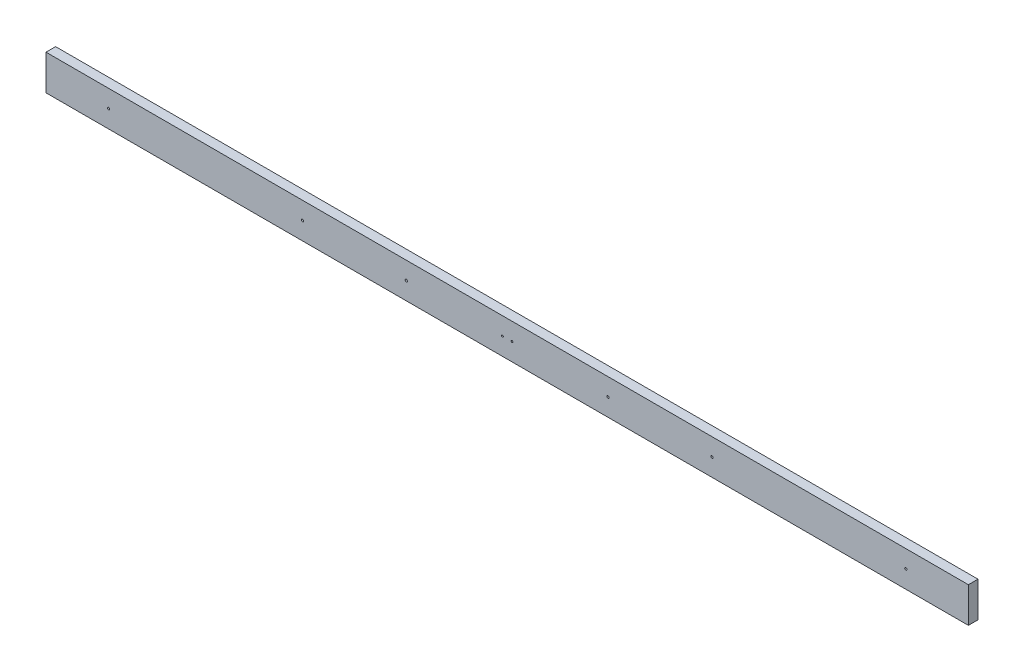
SolidWorks part; units mm, degrees
ref_plane "Front Plane" through (0, 0, 0) normal (0, 0, 1) x (1, 0, 0)
ref_plane "Top Plane" through (0, 0, 0) normal (0, 1, 0) x (1, 0, 0)
ref_plane "Right Plane" through (0, 0, 0) normal (1, 0, 0) x (0, 0, -1)
sketch "Sketch1" plane through (0, 0, 0) normal (0, 0, 1) x (1, 0, 0)
  line L1 (-1828.8, -69.85) -> (1828.8, -69.85)
  line L2 (-1828.8, -69.85) -> (-1828.8, 69.85)
  line L3 (-1828.8, 69.85) -> (1828.8, 69.85)
  line L4 (1828.8, -69.85) -> (1828.8, 69.85)
  line L5 (-1828.8, -69.85) -> (1828.8, 69.85) construction
  line L6 (-1828.8, 69.85) -> (1828.8, -69.85) construction
  point P0 (0, 0)
  dimension "D1" = 3657.6
  dimension "D2" = 139.7
extrude "Boss-Extrude1" add sketch "Sketch1" along normal blind 38.1
sketch "Sketch3" plane through (0, 0, 38.1) normal (0, 0, 1) x (1, 0, 0)
  line L0 (0, -69.85) -> (0, 69.85) construction
  line L1 (-1828.8, -69.85) -> (1828.8, -69.85) construction
  line L2 (1828.8, 69.85) -> (-1828.8, 69.85) construction
  line L3 (-25.4, -7.9375) -> (25.4, -7.9375) construction
  line L4 (-25.4, -7.9375) -> (-25.4, 7.9375) construction
  line L5 (-25.4, 7.9375) -> (25.4, 7.9375) construction
  line L6 (25.4, -7.9375) -> (25.4, 7.9375) construction
  line L7 (-19.05, 0) -> (19.05, 0) construction
  circle A0 centre (-19.05, 0) radius 3.5719
  circle A1 centre (19.05, 0) radius 3.5719
  point P14 (-25.4, 0)
  dimension "D8" = 7.1437
  dimension "D9" = 7.1437
  dimension "D1" = 15.875
  dimension "D2" = 7.9375
  dimension "D3" = 38.1
  dimension "D4" = 6.35
  dimension "D5" = 50.8
  dimension "D10" = 7.9375
extrude "Cut-Extrude2" cut sketch "Sketch3" against normal through all contours A0 | A1
sketch "Sketch4" plane through (0, 0, 38.1) normal (0, 0, 1) x (1, 0, 0)
  line L0 (0, 589.6071) -> (0, -768.8477)
  line L1 (762, 589.6071) -> (762, -768.8477)
  line L2 (0, 0) -> (-380, 0)
  line L3 (-380, 0) -> (-380, 478.8836)
  dimension "D1" = 762
  dimension "D2" = 380
sketch "Sketch5" plane through (0, 0, 38.1) normal (0, 0, 1) x (1, 0, 0)
  line L0 (-400, 0) -> (400, 0) construction
  circle A0 centre (400, 0) radius 4.4996
  circle A1 centre (-400, 0) radius 4.4996
  point P4 (0, 0)
  dimension "D2" = 8.9992
  dimension "D3" = 8.9992
  dimension "D1" = 800
extrude "Cut-Extrude3" cut sketch "Sketch5" against normal through all
sketch "Sketch6" plane through (0, 0, 38.1) normal (0, 0, 1) x (1, 0, 0)
  line L0 (1828.8, 0) -> (-1828.8, 0) construction
  line L1 (1828.8, -69.85) -> (1828.8, 69.85) construction
  line L2 (-1828.8, 69.85) -> (-1828.8, -69.85) construction
  line L3 (0, 69.85) -> (0, -69.85) construction
  line L4 (1828.8, 69.85) -> (-1828.8, 69.85) construction
  line L6 (-789.94, -403.86) -> (789.94, -403.86) construction
  line L7 (-789.94, -403.86) -> (-789.94, 403.86) construction
  line L8 (-789.94, 403.86) -> (789.94, 403.86) construction
  line L9 (789.94, -403.86) -> (789.94, 403.86) construction
  line L10 (-789.94, -403.86) -> (789.94, 403.86) construction
  line L11 (-789.94, 403.86) -> (789.94, -403.86) construction
  circle A0 centre (811.94, 0) radius 4.4996
  circle A1 centre (1580.6608, 0) radius 4.4996
  circle A3 centre (-1580.6608, 0) radius 4.4996
  circle A4 centre (-811.94, 0) radius 4.4996
  point P15 (400, 0)
  point P21 (0, 0)
  dimension "D2" = 8.9992
  dimension "D3" = 8.9992
  dimension "D1" = 768.7208
  dimension "D4" = 1579.88
  dimension "D5" = 807.72
  dimension "D6" = 22
extrude "Cut-Extrude4" cut sketch "Sketch6" against normal through all
sketch "Sketch7" plane through (0, 0, 38.1) normal (0, 0, 1) x (1, 0, 0)
  point P0 (-811.94, 0)
  point P1 (-1580.6608, 0)
  point P3 (400, 0)
  point P5 (811.94, 0)
  point P7 (1580.6608, 0)
equation "\"actuatorDistanceFromMiddle\" = 380"
equation "\"D2@Sketch4\"= \"actuatorDistanceFromMiddle\""
